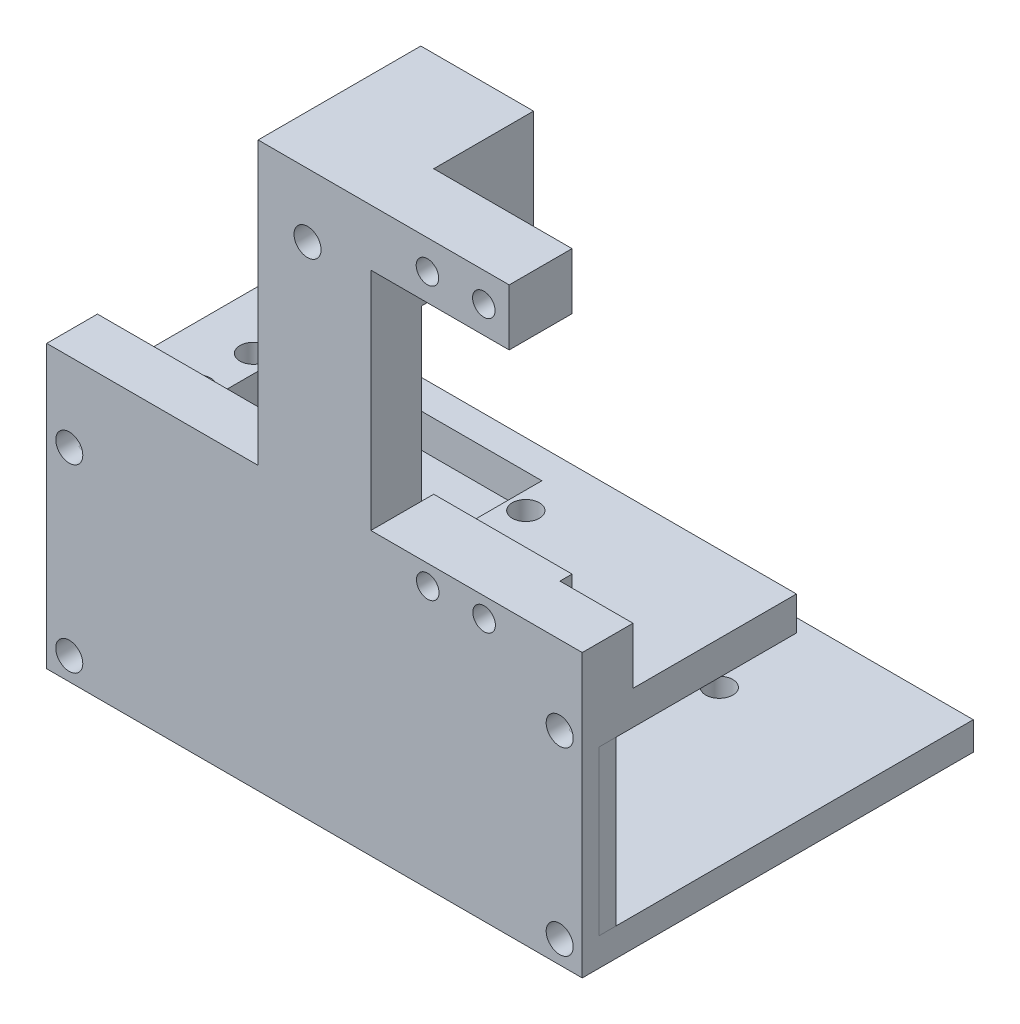
SolidWorks part; units mm, degrees
ref_plane "Front Plane" through (0, 0, 0) normal (0, 0, 1) x (1, 0, 0)
ref_plane "Top Plane" through (0, 0, 0) normal (0, 1, 0) x (1, 0, 0)
ref_plane "Right Plane" through (0, 0, 0) normal (1, 0, 0) x (0, 0, -1)
sketch "Sketch1" plane through (0, 0, 0) normal (0, 1, 0) x (1, 0, 0)
  line L8 (30, -25) -> (30, 20)
  line L9 (-45, 20) -> (30, 20)
  line L10 (-45, -25) -> (30, -25)
  line L11 (-45, 20) -> (-45, -25)
  point P0 (0, 0.6098)
  point P1 (0, 0)
  dimension "D1" = 45
  dimension "D2" = 75
extrude "Boss-Extrude1" add sketch "Sketch1" along normal blind 5
sketch "Sketch2" plane through (0, 5, 0) normal (0, 1, 0) x (1, 0, 0)
  circle A0 centre (-45.1238, -8.5547) radius 2.4
  circle A1 centre (-45.1238, 1.4453) radius 2.4
  circle A2 centre (3.1762, -8.5547) radius 2.4
  circle A3 centre (3.1762, 1.4453) radius 2.4
  dimension "D1" = 4.8
extrude "Cut-Extrude1" [suppressed] cut sketch "Sketch2" against normal blind 5 and the other way through all
sketch "Sketch3" plane through (0, 5, 0) normal (0, 1, 0) x (1, 0, 0)
  line L5 (30, -25) -> (30, 20) construction
  line L6 (-45, 20) -> (30, 20)
  line L7 (-45, 20) -> (-45, 16)
  line L8 (-45, 16) -> (30, 16)
  line L9 (30, 20) -> (30, 16)
  dimension "D1" = 4
extrude "Boss-Extrude3" add sketch "Sketch3" along normal blind 24
sketch "Sketch4" plane through (0, 0, -20) normal (0, 0, -1) x (-1, 0, 0)
  line L0 (45, 29) -> (45, 0) construction
  line L1 (-30, 29) -> (45, 29)
  line L2 (-30, 29) -> (-30, 24)
  line L3 (-30, 24) -> (45, 24)
  line L4 (45, 29) -> (45, 24)
  dimension "D1" = 5
extrude "Boss-Extrude4" add sketch "Sketch4" along normal blind 24
sketch "Sketch6" plane through (0, 29, 0) normal (0, 1, 0) x (1, 0, 0)
  line L5 (-7.5, 26.45) -> (-7.5, 16) construction
  line L6 (-45, 16) -> (30, 16) construction
  line L7 (-27.5, 26.45) -> (12.5, 26.45)
  circle A2 centre (12.5, 26.45) radius 1.6
  circle A3 centre (-27.5, 26.45) radius 1.6
  point P13 (-7.5, 26.45)
  dimension "10" = 10.45
sketch "Sketch9" plane through (0, 29, 0) normal (0, 1, 0) x (1, 0, 0)
  circle A0 centre (-27.5, 26.45) radius 2.4
  circle A1 centre (12.5, 26.45) radius 2.4
  dimension "D1" = 4.8
  dimension "D2" = 4.8
extrude "Cut-Extrude3" cut sketch "Sketch9" against normal through all contours A0 | A1
sketch "Sketch10" plane through (0, 5, 0) normal (0, 1, 0) x (1, 0, 0)
  line L0 (-41.9738, -14.5547) -> (-41.9738, 7.4453)
  line L5 (-40.9738, -13.5547) -> (-0.9738, -13.5547)
  line L6 (-40.9738, -13.5547) -> (-40.9738, 6.4453)
  line L7 (-40.9738, 6.4453) -> (-0.9738, 6.4453)
  line L8 (-0.9738, -13.5547) -> (-0.9738, 6.4453)
  line L9 (-41.9738, 7.4453) -> (0.0262, 7.4453)
  line L10 (0.0262, -14.5547) -> (0.0262, 7.4453)
  line L11 (-41.9738, -14.5547) -> (0.0262, -14.5547)
  dimension "D1" = 1
extrude "Cut-Extrude4" [suppressed] cut sketch "Sketch10" against normal through all contours L0 L9 L10 L11
chamfer "Chamfer1" distance 5 angle 45 1 edges at (-7.5, 5, -16)
chamfer "Chamfer2" distance 5 angle 45 1 edges at (-7.5, 24, -20)
fillet "Fillet1" [suppressed] radius 5
sketch "Sketch13" plane through (0, 5, 0) normal (0, 1, 0) x (1, 0, 0)
  line L1 (-45, 11) -> (30, 11)
  line L2 (-45, 11) -> (-45, -25.3668)
  line L3 (-45, -25.3668) -> (30, -25.3668)
  line L4 (30, 11) -> (30, -25.3668)
extrude "Boss-Extrude6" add sketch "Sketch13" against normal blind 10 from offset 63 separate body
sketch "Sketch14" plane through (0, 68, 0) normal (0, 1, 0) x (1, 0, 0)
  circle A0 centre (-45.1238, -8.5547) radius 2.4
  circle A9 centre (-45.1238, 1.4453) radius 2.4
  circle A10 centre (3.1762, 1.4453) radius 2.4
  circle A11 centre (3.1762, -8.5547) radius 2.4
extrude "Cut-Extrude5" cut sketch "Sketch14" against normal through all
sketch "Sketch15" plane through (0, 68, 0) normal (0, 1, 0) x (1, 0, 0)
  line L12 (-41.9738, 7.4453) -> (-41.9738, -14.5547)
  line L13 (0.0262, 7.4453) -> (-41.9738, 7.4453)
  line L14 (0.0262, -14.5547) -> (0.0262, 7.4453)
  line L15 (-41.9738, -14.5547) -> (0.0262, -14.5547)
  line L16 (-41.9738, 7.4453) -> (-41.9738, -14.5547)
  line L17 (0.0262, 7.4453) -> (-41.9738, 7.4453)
  line L18 (0.0262, -14.5547) -> (0.0262, 7.4453)
  line L19 (-41.9738, -14.5547) -> (0.0262, -14.5547)
  dimension "D2" = 0
extrude "Cut-Extrude6" cut sketch "Sketch15" against normal through all
sketch "Sketch16" plane through (0, 0, -16) normal (0, 0, 1) x (1, 0, 0)
  line L0 (30, 29) -> (30, 10) construction
  line L1 (-45, 29) -> (30, 29)
  line L2 (-45, 29) -> (-45, 24)
  line L3 (-45, 24) -> (30, 24)
  line L4 (30, 29) -> (30, 24)
  dimension "D1" = 5
extrude "Boss-Extrude7" add sketch "Sketch16" along normal blind 39
sketch "Sketch17" plane through (-45, 0, 0) normal (-1, 0, 0) x (0, 0, 1)
  line L0 (-20, 0) -> (25, 0) construction
  line L1 (-44, 24) -> (25, 24)
  line L2 (-44, 24) -> (-44, 0)
  line L3 (-44, 0) -> (25, 0)
  line L4 (25, 24) -> (25, 0)
extrude "Cut-Extrude7" cut sketch "Sketch17" against normal through all
sketch "Sketch18" plane through (0, 58, 0) normal (0, -1, 0) x (1, 0, 0)
  line L0 (30, 25.3668) -> (30, -11) construction
  line L5 (-45, 25.3668) -> (30, 25.3668)
  line L6 (-45, 25.3668) -> (-45, 22.3668)
  line L7 (-45, 22.3668) -> (30, 22.3668)
  line L8 (30, 25.3668) -> (30, 22.3668)
  dimension "D1" = 3
extrude "Boss-Extrude8" add sketch "Sketch18" along normal blind 34
sketch "Sketch20" plane through (0, 29, 0) normal (0, 1, 0) x (1, 0, 0)
  line L2 (-47.1238, 5.4453) -> (-47.1238, -15.6262)
  line L3 (-47.1238, -15.6262) -> (7.6092, -15.6262)
  line L6 (-17.6474, 9.3738) -> (7.6092, 9.3738)
  line L7 (7.6092, 9.3738) -> (7.6092, -15.6262)
  arc A1 (-17.6474, 9.3738) -> (-47.1238, 5.4453) centre (-32.1238, 5.4453) ccw
  dimension "D1" = 15
  dimension "D2" = 25
extrude "Cut-Extrude8" cut sketch "Sketch20" against normal through all
sketch "Sketch21" plane through (0, 24, 0) normal (0, -1, 0) x (-1, 0, 0)
  circle A0 centre (30.9738, -3.5547) radius 20
extrude "Cut-Extrude9" cut sketch "Sketch21" against normal blind 9
sketch "Sketch22" plane through (0, 29, 0) normal (0, 1, 0) x (1, 0, 0)
  line L0 (30, 37.1801) -> (-7.5, 37.1801)
  line L1 (30, -23) -> (30, 44) construction
sketch "Sketch23" plane through (-45, 0, 0) normal (-1, 0, 0) x (0, 0, 1)
  line L1 (-44, 29) -> (25.3668, 29)
  line L2 (-44, 29) -> (-44, 24)
  line L3 (-44, 24) -> (25.3668, 24)
  line L4 (25.3668, 29) -> (25.3668, 24)
extrude "Boss-Extrude9" add sketch "Sketch23" along normal blind 10
sketch "Sketch24" plane through (-45, 0, 0) normal (-1, 0, 0) x (0, 0, 1)
  line L0 (25.3668, 29) -> (25.3668, 68) construction
  line L1 (-11, 68) -> (25.3668, 68)
  line L2 (-11, 68) -> (-11, 58)
  line L3 (-11, 58) -> (25.3668, 58)
  line L4 (25.3668, 68) -> (25.3668, 58)
extrude "Boss-Extrude10" add sketch "Sketch24" along normal blind 10
sketch "Sketch25" plane through (0, 68, 0) normal (0, 1, 0) x (1, 0, 0)
  circle A1 centre (3.1762, 1.4453) radius 2.4
  circle A2 centre (3.1762, 1.4453) radius 2.4
  circle A3 centre (3.1762, -8.5547) radius 2.4
  circle A4 centre (3.1762, -8.5547) radius 2.4
  circle A5 centre (-45.1238, 1.4453) radius 2.4
  circle A6 centre (-45.1238, 1.4453) radius 2.4
  circle A7 centre (-45.1238, -8.5547) radius 2.4
  circle A8 centre (-45.1238, -8.5547) radius 2.4
  dimension "D1" = 0
  dimension "D2" = 0
  dimension "D3" = 0
  dimension "D4" = 0
extrude "Cut-Extrude10" cut sketch "Sketch25" against normal blind 10
sketch "Sketch26" plane through (0, 24, 0) normal (0, -1, 0) x (1, 0, 0)
  circle A1 centre (-30.9738, 3.5547) radius 20
  circle A2 centre (-30.9738, 3.5547) radius 20
  dimension "D1" = 0
extrude "Cut-Extrude11" cut sketch "Sketch26" against normal blind 10
sketch "Sketch27" plane through (30, 0, 0) normal (1, 0, 0) x (0, 0, -1)
  line L1 (44, 24) -> (-25.3668, 24)
  line L2 (44, 24) -> (44, 29)
  line L3 (44, 29) -> (-25.3668, 29)
  line L4 (-25.3668, 24) -> (-25.3668, 29)
extrude "Boss-Extrude11" add sketch "Sketch27" along normal blind 10
sketch "Sketch28" plane through (-55, 0, 0) normal (-1, 0, 0) x (0, 0, 1)
  line L6 (-11, 68) -> (25.3668, 68)
  line L7 (-11, 68) -> (-11, 64)
  line L9 (25.3668, 68) -> (25.3668, 64)
  line L10 (-11, 64) -> (25.3668, 64)
  dimension "D1" = 4
extrude "Cut-Extrude12" cut sketch "Sketch28" against normal through all
sketch "Sketch29" plane through (0, 0, 25.3668) normal (0, 0, 1) x (1, 0, 0)
  line L5 (-55, 64) -> (40, 64)
  line L6 (-55, 64) -> (-55, 24)
  line L7 (-55, 24) -> (40, 24)
  line L8 (40, 64) -> (40, 24)
extrude "Boss-Extrude13" add sketch "Sketch29" against normal blind 3
sketch "Sketch30" plane through (0, 0, 22.3668) normal (0, 0, -1) x (-1, 0, 0)
  line L1 (-40, 64) -> (-30, 64)
  line L2 (-40, 64) -> (-40, 58)
  line L3 (-40, 58) -> (-30, 58)
  line L4 (-30, 64) -> (-30, 58)
extrude "Boss-Extrude14" add sketch "Sketch30" along normal blind 35
sketch "Sketch31" plane through (0, 0, -11) normal (0, 0, -1) x (-1, 0, 0)
  line L1 (-30, 64) -> (55, 64)
  line L2 (-30, 64) -> (-30, 58)
  line L3 (-30, 58) -> (55, 58)
  line L4 (55, 64) -> (55, 58)
extrude "Boss-Extrude15" add sketch "Sketch31" along normal blind 1.632
sketch "Sketch34" plane through (0, 0, 25.3668) normal (0, 0, 1) x (1, 0, 0)
  line L0 (-51, 60) -> (-51, 28)
  line L1 (-55, 64) -> (40, 64)
  line L2 (-55, 64) -> (-55, 24)
  line L3 (-55, 24) -> (40, 24)
  line L4 (40, 64) -> (40, 24)
  line L5 (-51, 28) -> (36, 28)
  line L6 (36, 60) -> (36, 28)
  line L7 (-51, 60) -> (36, 60)
  circle A0 centre (-51, 60) radius 2.4
  circle A1 centre (36, 60) radius 2.4
  circle A2 centre (-51, 28) radius 2.4
  circle A3 centre (36, 28) radius 2.4
  dimension "D2" = 4.8
  dimension "D3" = 4.8
  dimension "D4" = 4.8
  dimension "D5" = 4.8
  dimension "D1" = 4
extrude "Cut-Extrude13" cut sketch "Sketch34" against normal blind 6 contours A0 | A2 | A3 | A1
sketch "Sketch35" plane through (0, 0, 22.3668) normal (0, 0, -1) x (-1, 0, 0)
  line L1 (-40, 58) -> (55, 58)
  line L2 (-40, 58) -> (-40, 29)
  line L3 (-40, 29) -> (55, 29)
  line L4 (55, 58) -> (55, 29)
extrude "Boss-Extrude18" add sketch "Sketch35" along normal blind 3 separate body
sketch "Sketch37" plane through (0, 24, 0) normal (0, -1, 0) x (1, 0, 0)
  circle A1 centre (-30.9738, 3.5547) radius 20
  circle A2 centre (-30.9738, 3.5547) radius 20
  dimension "D1" = 0
extrude "Cut-Extrude14" cut sketch "Sketch37" against normal up to surface (34 mm away) up to face at (-2.1429, 58, 11.5098)
sketch "Sketch38" plane through (0, 0, 25.3668) normal (0, 0, 1) x (1, 0, 0)
  line L4 (40, 64) -> (-55, 64)
  line L5 (40, 24) -> (40, 64)
  line L6 (-55, 24) -> (40, 24)
  line L7 (-55, 64) -> (-55, 24)
  line L8 (40, 64) -> (-55, 64)
  line L9 (40, 24) -> (40, 64)
  line L10 (-55, 24) -> (40, 24)
  line L11 (-55, 64) -> (-55, 24)
  line L12 (-51, 60) -> (-51, 28)
  line L13 (-51, 28) -> (36, 28)
  line L14 (36, 28) -> (36, 60)
  line L15 (36, 60) -> (-51, 60)
  line L16 (-51, 60) -> (-51, 28)
  line L17 (-51, 28) -> (36, 28)
  line L18 (36, 28) -> (36, 60)
  line L19 (36, 60) -> (-51, 60)
  circle A1 centre (36, 28) radius 2.4
  circle A2 centre (36, 28) radius 2.4
  circle A3 centre (-51, 28) radius 2.4
  circle A4 centre (-51, 28) radius 2.4
  circle A5 centre (36, 60) radius 2.4
  circle A6 centre (36, 60) radius 2.4
  circle A7 centre (-51, 60) radius 2.4
  circle A8 centre (-51, 60) radius 2.4
  dimension "D1" = 0
  dimension "D2" = 0
  dimension "D3" = 0
  dimension "D4" = 0
  dimension "D5" = 0
  dimension "D6" = 0
extrude "Cut-Extrude15" cut sketch "Sketch38" against normal blind 6 contours A8 | A4 | A6 | A2
fillet "Fillet2" [suppressed] radius 5
sketch "Sketch39" plane through (0, 64, 0) normal (0, 1, 0) x (1, 0, 0)
  line L0 (-55, 12.632) -> (-55, -25.3668) construction
  line L1 (-55, -16.3668) -> (40, -16.3668)
  line L2 (-55, -16.3668) -> (-55, -25.3668)
  line L3 (-55, -25.3668) -> (40, -25.3668)
  line L4 (40, -16.3668) -> (40, -25.3668)
  dimension "D1" = 9
extrude "Boss-Extrude19" add sketch "Sketch39" along normal blind 10
ref_plane "Plane1" [suppressed] through (0, 0, 20) normal (0, 0, 1) x (1, 0, 0)
sketch "Sketch41" plane through (40, 0, 0) normal (1, 0, 0) x (0, 0, -1)
  line L0 (-16.3668, 74) -> (-16.3668, 64) construction
  line L1 (-25.3668, 74) -> (-16.3668, 74)
  line L2 (-25.3668, 74) -> (-25.3668, 4)
  line L3 (-25.3668, 4) -> (-16.3668, 4)
  line L4 (-16.3668, 74) -> (-16.3668, 4)
  dimension "D1" = 70
extrude "Boss-Extrude20" [suppressed] add sketch "Sketch41" along normal blind 30
sketch "Sketch42" [suppressed] plane through (0, 0, 16.3668) normal (0, 0, -1) x (-1, 0, 0)
  line L0 (-70, 174) -> (-40, 104)
  line L1 (-40, 104) -> (-70, 104)
  line L2 (-70, 104) -> (-70, 174)
extrude "Cut-Extrude16" [suppressed] cut sketch "Sketch42" against normal blind 30
sketch "Sketch43" plane through (-55, 0, 0) normal (-1, 0, 0) x (0, 0, 1)
  line L0 (25.3668, 24) -> (25.3668, 74) construction
  line L1 (16.3668, 74) -> (25.3668, 74)
  line L2 (16.3668, 74) -> (16.3668, 4)
  line L3 (16.3668, 4) -> (25.3668, 4)
  line L4 (25.3668, 74) -> (25.3668, 4)
  dimension "D1" = 70
extrude "Boss-Extrude21" [suppressed] add sketch "Sketch43" along normal blind 10
sketch "Sketch44" [suppressed] plane through (0, 0, 16.3668) normal (0, 0, -1) x (-1, 0, 0)
  line L0 (65, 174) -> (55, 104)
  line L1 (55, 104) -> (65, 104)
  line L2 (65, 104) -> (65, 174)
extrude "Cut-Extrude17" [suppressed] cut sketch "Sketch44" against normal blind 10
sketch "Sketch46" plane through (0, 64, 0) normal (0, 1, 0) x (1, 0, 0)
  line L0 (40, 12.6332) -> (40, -16.3668) construction
  line L1 (-55, 12.632) -> (40, 12.632)
  line L2 (-55, 12.632) -> (-55, 8.632)
  line L3 (-55, 8.632) -> (40, 8.632)
  line L4 (40, 12.632) -> (40, 8.632)
  dimension "D1" = 4
extrude "Boss-Extrude22" [suppressed] add sketch "Sketch46" along normal up to surface (110 mm away)
sketch "Sketch48" plane through (-55, 0, 0) normal (-1, 0, 0) x (0, 0, 1)
  line L0 (-44, 24) -> (25.3668, 24) construction
  line L1 (-44, 29) -> (-24, 29)
  line L2 (-44, 29) -> (-44, 24)
  line L3 (-44, 24) -> (-24, 24)
  line L4 (-24, 29) -> (-24, 24)
  dimension "D1" = 20
extrude "Boss-Extrude23" [suppressed] add sketch "Sketch48" along normal blind 5
sketch "Sketch49" [suppressed] plane through (0, 29, 0) normal (0, 1, 0) x (1, 0, 0)
  line L1 (-60, 44) -> (-55, 44)
  line L2 (-60, 44) -> (-60, 24)
  line L3 (-60, 24) -> (-55, 24)
  line L4 (-55, 44) -> (-55, 24)
extrude "Boss-Extrude24" [suppressed] add sketch "Sketch49" along normal blind 50
sketch "Sketch50" plane through (40, 0, 0) normal (1, 0, 0) x (0, 0, -1)
  line L0 (-25.3668, 24) -> (44, 24) construction
  line L1 (44, 29) -> (24, 29)
  line L2 (44, 29) -> (44, 24)
  line L3 (44, 24) -> (24, 24)
  line L4 (24, 29) -> (24, 24)
extrude "Boss-Extrude25" [suppressed] add sketch "Sketch50" along normal blind 5
sketch "Sketch51" [suppressed] plane through (0, 29, 0) normal (0, 1, 0) x (1, 0, 0)
  line L1 (40, 24) -> (45, 24)
  line L2 (40, 24) -> (40, 44)
  line L3 (40, 44) -> (45, 44)
  line L4 (45, 24) -> (45, 44)
extrude "Boss-Extrude26" [suppressed] add sketch "Sketch51" along normal up to surface (50 mm away)
sketch "Sketch52" [suppressed] plane through (0, 0, -44) normal (0, 0, -1) x (-1, 0, 0)
  line L5 (-45, 79) -> (-40, 79)
  line L6 (-45, 79) -> (-45, 58)
  line L7 (-45, 58) -> (-40, 58)
  line L8 (-40, 79) -> (-40, 58)
  line L9 (60, 79) -> (55, 79)
  line L10 (60, 79) -> (60, 58)
  line L11 (60, 58) -> (55, 58)
  line L12 (55, 79) -> (55, 58)
extrude "Boss-Extrude27" [suppressed] add sketch "Sketch52" along normal blind 30
sketch "Sketch53" [suppressed] plane through (40, 0, 0) normal (-1, 0, 0) x (0, 0, 1)
  line L0 (-24, 79) -> (-24, 29) construction
  line L1 (-44, 79) -> (-24, 79)
  line L2 (-44, 79) -> (-44, 74)
  line L3 (-44, 74) -> (-24, 74)
  line L4 (-24, 79) -> (-24, 74)
  dimension "D1" = 5
extrude "Boss-Extrude28" [suppressed] add sketch "Sketch53" along normal up to surface (95 mm away)
sketch "Sketch54" plane through (0, 74, 0) normal (0, 1, 0) x (1, 0, 0)
  line L0 (-7.5, -25.3668) -> (-7.5, -16.3668)
  line L1 (-55, -25.3668) -> (40, -25.3668) construction
  line L2 (40, -16.3668) -> (-55, -16.3668) construction
  line L3 (-7.5, -16.3668) -> (-17.5, -16.3668)
  line L4 (40, -16.3668) -> (-55, -16.3668) construction
  line L5 (-17.5, -16.3668) -> (-17.5, -25.3668)
  line L6 (-17.5, -25.3668) -> (-7.5, -25.3668)
  line L7 (-7.5, -16.3668) -> (2.5, -16.3668)
  line L8 (2.5, -16.3668) -> (2.5, -25.3668)
  line L9 (2.5, -25.3668) -> (-7.5, -25.3668)
  line M5 (-55, -25.3668) -> (40, -25.3668)
  line M7 (40, -16.3668) -> (-55, -16.3668)
  dimension "D1" = 10
  dimension "D2" = 10
extrude "Boss-Extrude29" add sketch "Sketch54" along normal blind 50 contours L5 L0 M7 M5 | L8 L0 M7 M5 region at (-12.5, 74, 20.8668) region at (-2.5, 74, 20.8668)
sketch "Sketch55" plane through (0, 0, 16.3668) normal (0, 0, -1) x (-1, 0, 0)
  line L0 (17.5, 124) -> (17.5, 74) construction
  line L1 (-2.5, 124) -> (17.5, 124)
  line L2 (-2.5, 124) -> (-2.5, 104)
  line L3 (-2.5, 104) -> (17.5, 104)
  line L4 (17.5, 124) -> (17.5, 104)
  dimension "D1" = 20
extrude "Boss-Extrude30" add sketch "Sketch55" along normal blind 19.86
sketch "Sketch56" plane through (0, 0, -3.4932) normal (0, 0, -1) x (-1, 0, 0)
  circle A1 centre (8.7322, 112.7087) radius 2.4
extrude "Cut-Extrude18" cut sketch "Sketch56" against normal through all
sketch "Sketch57" plane through (2.5, 0, 0) normal (1, 0, 0) x (0, 0, -1)
  line L6 (-25.3668, 124) -> (-14.2168, 124)
  line L7 (-25.3668, 124) -> (-25.3668, 114)
  line L8 (-25.3668, 114) -> (-14.2168, 114)
  line L9 (-14.2168, 124) -> (-14.2168, 114)
  dimension "D1" = 11.15
  dimension "D2" = 10
extrude "Boss-Extrude31" add sketch "Sketch57" along normal blind 24.54
sketch "Sketch58" plane through (0, 0, 16.3668) normal (0, 0, -1) x (-1, 0, 0)
  line L0 (-40, 74) -> (-2.5, 74) construction
  line L1 (-27.04, 74) -> (-2.5, 74)
  line L2 (-27.04, 74) -> (-27.04, 64)
  line L3 (-27.04, 64) -> (-2.5, 64)
  line L4 (-2.5, 74) -> (-2.5, 64)
  line L5 (-40, 64) -> (55, 64) construction
extrude "Boss-Extrude32" add sketch "Sketch58" along normal blind 2.15
sketch "Sketch59" plane through (0, 0, 25.3668) normal (0, 0, 1) x (1, 0, 0)
  circle A0 centre (12.5395, 118.7779) radius 2
  circle A1 centre (22.5394, 118.7892) radius 2
  circle A2 centre (12.5941, 70.4779) radius 2
  circle A3 centre (22.5941, 70.4892) radius 2
extrude "Cut-Extrude19" cut sketch "Sketch59" against normal through all
